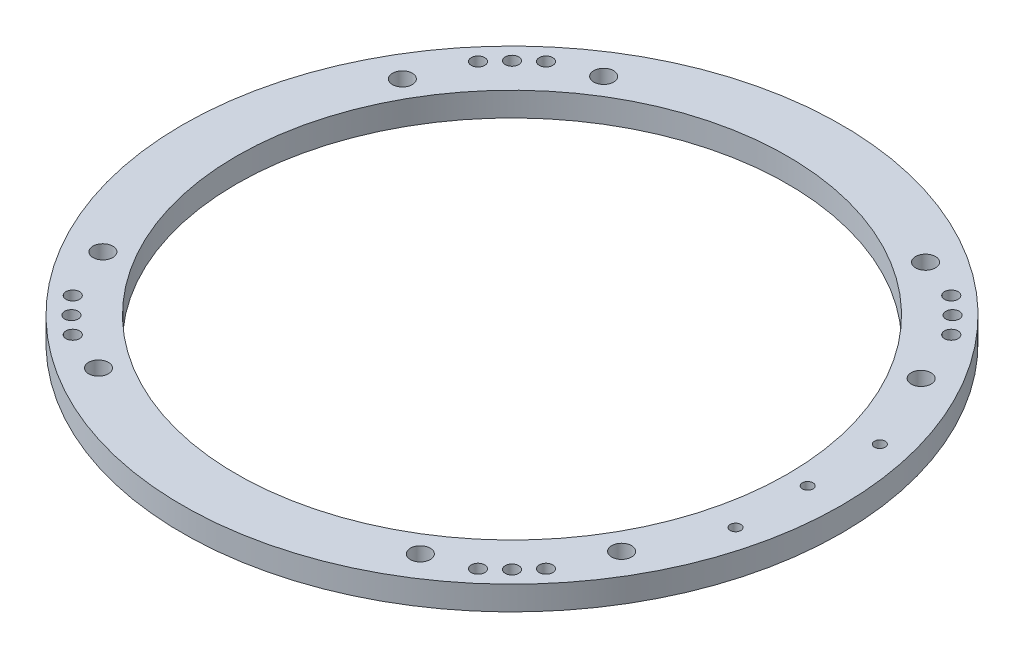
SolidWorks part; units mm, degrees
material "Oak"
ref_plane "Front Plane" through (0, 0, 0) normal (0, 0, 1) x (1, 0, 0)
ref_plane "Top Plane" through (0, 0, 0) normal (0, 1, 0) x (1, 0, 0)
ref_plane "Right Plane" through (0, 0, 0) normal (1, 0, 0) x (0, 0, -1)
sketch "Sketch1" plane through (0, 0, 0) normal (0, 0, 1) x (1, 0, 0)
  line L0 (0, 1125.8152) -> (0, -48874.1848) construction
  line L1 (145.5262, 1052.195) -> (152.4, 1052.195)
  line L9 (145.5262, 1064.895) -> (174.1012, 1064.895)
  line L10 (145.5262, 1064.895) -> (145.5262, 1052.195)
  line L11 (145.5262, 1052.195) -> (174.1012, 1052.195)
  line L12 (174.1012, 1064.895) -> (174.1012, 1052.195)
revolve "Revolve1" add sketch "Sketch1" angle 360 about L0 region at (159.8137, 1058.545, 0)
hole_wizard "9/32 (0.28125) Diameter Hole1" positions "Sketch9" profile "Sketch10" hole size "9/32" standard "ANSI Inch" end condition through all
sketch "Sketch9" plane through (0, 1052.195, 0) normal (0, -1, 0) x (-1, 0, 0)
  line L0 (0, 0) -> (116.373, 116.373) construction
  line L3 (0, 0) -> (107.0457, 125.0062) construction
  arc A0 (107.0457, 125.0062) -> (125.0062, 107.0457) centre (0, 0) cw
  circle A1 centre (0, 0) radius 164.5762 construction
  point P0 (107.0457, 125.0062)
  point P2 (125.0062, 107.0457)
  point P15 (116.373, 116.373)
sketch "Sketch10" plane through (-107.0457, 1052.195, -125.0062) normal (1, 0, 0) x (0, 0, -1)
  line L0 (0, 0) -> (0, 12.7)
  line L1 (0, 12.7) -> (3.5719, 12.7)
  line L2 (3.5719, 12.7) -> (3.5719, 0)
  line L5 (3.5719, 0) -> (0, 0)
  line L11 (0, -6.35) -> (0, 107.95) construction
  dimension "Thru Hole Dia." = 7.1437
  dimension "Thru Hole Depth" = 12.7
pattern_circular "CirPattern1" count 4 over 360 about axis through (0, 1125.8152, 0) along (0, 1, 0) of "9/32 (0.28125) Diameter Hole1"
ref_plane "Plane1" through (0, 1058.545, 0) normal (0, 1, 0) x (1, 0, 0)
hole_wizard "#10 Clearance Hole1" positions "Sketch14" profile "Sketch15" hole size "#10" standard "ANSI Inch" end condition through all
sketch "Sketch14" plane through (0, 1064.895, 0) normal (0, 1, 0) x (1, 0, 0)
  point P0 (156.21, 38.1)
  point P3 (156.21, 0)
  point P6 (156.21, -38.1)
sketch "Sketch15" plane through (156.21, 1064.895, -38.1) normal (1, 0, 0) x (0, 0, 1)
  line L0 (0, 0) -> (0, 12.7)
  line L1 (0, 12.7) -> (2.8067, 12.7)
  line L2 (2.8067, 12.7) -> (2.8067, 0)
  line L5 (2.8067, 0) -> (0, 0)
  line L11 (0, -6.35) -> (0, 107.95) construction
  dimension "Thru Hole Dia." = 5.6134
  dimension "Thru Hole Depth" = 12.7
hole_wizard "Z (0.413) Diameter Hole1" positions "Sketch16" profile "Sketch17" hole size "Z" standard "ANSI Inch" end condition through all
sketch "Sketch16" plane through (0, 1064.895, 0) normal (0, 1, 0) x (1, 0, 0)
  line L0 (-137.0279, -79.1131) -> (137.0279, 79.1131) construction
  line L4 (137.0279, -79.1131) -> (-137.0279, 79.1131) construction
  line L6 (0, 0) -> (0, 158.2262) construction
  line L8 (-85.0149, -133.4467) -> (85.0149, 133.4467) construction
  line L11 (-85.0149, 133.4467) -> (85.0149, -133.4467) construction
  circle A0 centre (0, 0) radius 158.2262 construction
  circle A1 centre (0, 0) radius 145.5262 construction
  point P0 (-137.0279, -79.1131)
  point P2 (137.0279, -79.1131)
  point P4 (137.0279, 79.1131)
  point P6 (-137.0279, 79.1131)
  point P37 (-85.0149, 133.4467)
  point P39 (85.0149, 133.4467)
  point P41 (85.0149, -133.4467)
  point P43 (-85.0149, -133.4467)
  dimension "D2" = 12.7
  dimension "D1" = 120
  dimension "D3" = 65
sketch "Sketch17" plane through (-137.0279, 1064.895, 79.1131) normal (1, 0, 0) x (0, 0, 1)
  line L0 (0, 0) -> (0, 12.7)
  line L1 (0, 12.7) -> (5.2451, 12.7)
  line L2 (5.2451, 12.7) -> (5.2451, 0)
  line L5 (5.2451, 0) -> (0, 0)
  line L11 (0, -6.35) -> (0, 107.95) construction
  dimension "Thru Hole Dia." = 10.4902
  dimension "Thru Hole Depth" = 12.7
